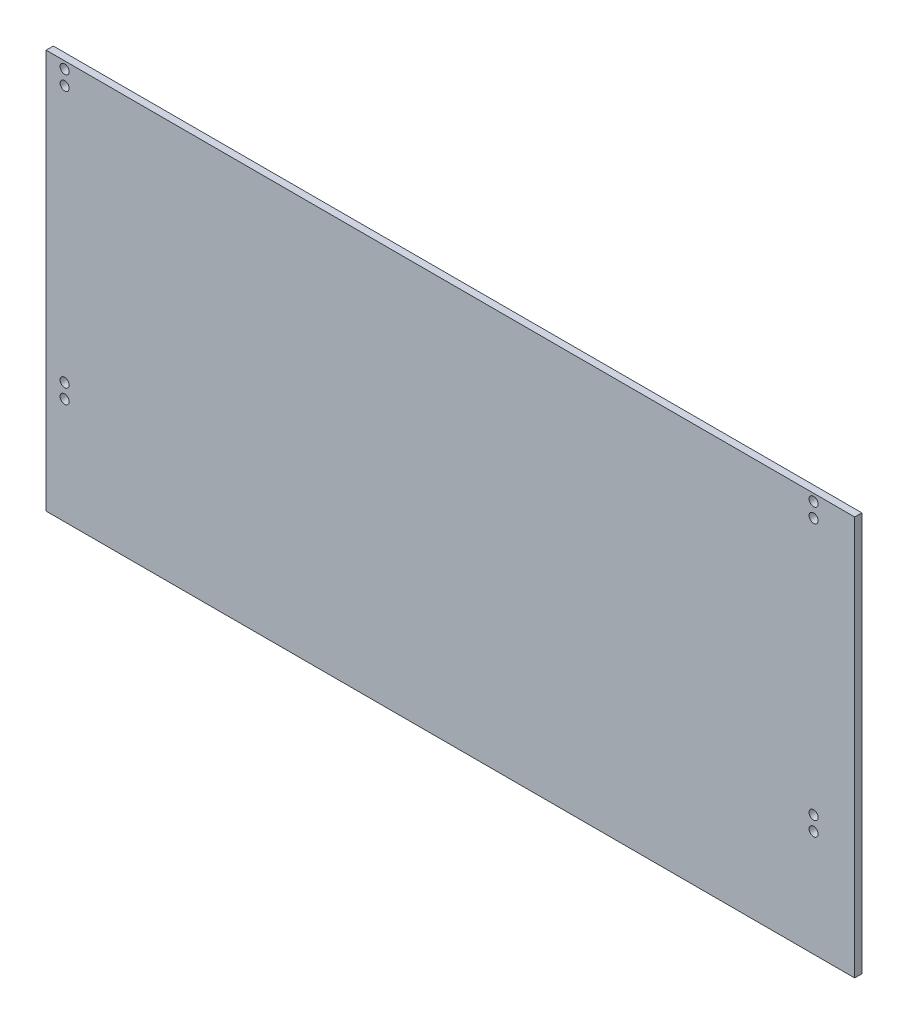
SolidWorks part; units mm, degrees
material "ABS"
ref_plane "X-Y Datum" through (0, 0, 0) normal (0, 0, 1) x (1, 0, 0)
ref_plane "X-Z Datum" through (0, 0, 0) normal (0, 1, 0) x (1, 0, 0)
ref_plane "Y-Z Datum" through (0, 0, 0) normal (1, 0, 0) x (0, 0, -1)
sketch "Sketch1" plane through (0, 0, 0) normal (0, 0, 1) x (1, 0, 0)
  line L0 (-178.775, 88.275) -> (-178.775, -88.275)
  line L1 (-178.775, 88.275) -> (178.775, 88.275)
  line L2 (-178.775, 88.275) -> (-178.775, -88.275)
  line L3 (-178.775, -88.275) -> (178.775, -88.275)
  line L4 (178.775, 88.275) -> (178.775, -88.275)
  line L5 (-178.775, 88.275) -> (178.775, -88.275) construction
  line L6 (-178.775, -88.275) -> (178.775, 88.275) construction
  line L7 (-178.775, -88.275) -> (178.775, -88.275)
  line L8 (178.775, 88.275) -> (178.775, -88.275)
  line L9 (-178.775, 88.275) -> (178.775, 88.275)
  circle A0 centre (-168, -77.5) radius 10.775
  circle A1 centre (-144, -77.5) radius 10.775 construction
  circle A2 centre (-156, -54.5) radius 10.775
  point P0 (0, 0)
  dimension "D1" = 21.55
  dimension "D2" = 24
  dimension "D3" = 23
  dimension "D4" = 12
  dimension "D5" = 176.55
  dimension "D6" = 357.55
  dimension "D7" = 0
extrude "Boss-Extrude1" add sketch "Sketch1" along normal blind 3.175 contours A0 L3 L4 L1 L2 A2 | A2 | A0 | A0 L2 L3 | L9 L0 L7 L8 L1 L4 L3 L2 region at (1.9652, 0.8062, 0) region at (-176.3682, -85.8682, 0) region at (-168, -77.5, 0) region at (-156, -54.5, 0)
sketch "Sketch2" plane through (0, 0, 0) normal (0, 0, -1) x (-1, 0, 0)
  circle A0 centre (170.6, 85.1) radius 2 construction
  circle A1 centre (170.6, 78.75) radius 2 construction
  circle A2 centre (170.6, -34.9) radius 2 construction
  circle A3 centre (170.6, -41.25) radius 2 construction
  circle A4 centre (-160.6, 85.1) radius 2 construction
  circle A5 centre (-160.6, 78.75) radius 2 construction
  circle A6 centre (-160.6, -34.9) radius 2 construction
  circle A7 centre (-160.6, -41.25) radius 2 construction
  circle A8 centre (170.6, 85.1) radius 2
  circle A9 centre (170.6, 78.75) radius 2
  circle A10 centre (170.6, -34.9) radius 2
  circle A11 centre (170.6, -41.25) radius 2
  circle A12 centre (-160.6, 85.1) radius 2
  circle A13 centre (-160.6, 78.75) radius 2
  circle A14 centre (-160.6, -34.9) radius 2
  circle A15 centre (-160.6, -41.25) radius 2
extrude "Cut-Extrude1" cut sketch "Sketch2" against normal through all
